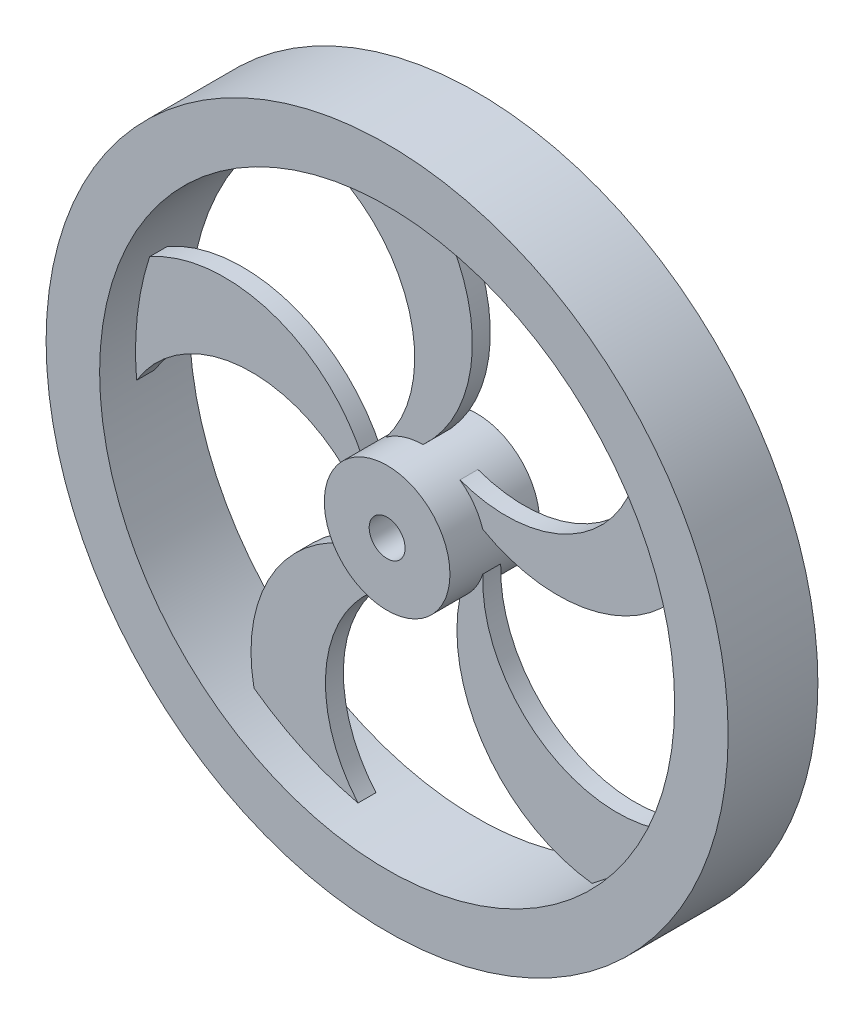
SolidWorks part; units mm, degrees
ref_plane "Front Plane" through (0, 0, 0) normal (0, 0, 1) x (1, 0, 0)
ref_plane "Top Plane" through (0, 0, 0) normal (0, 1, 0) x (1, 0, 0)
ref_plane "Right Plane" through (0, 0, 0) normal (1, 0, 0) x (0, 0, -1)
sketch "Sketch1" plane through (0, 0, 0) normal (0, 0, 1) x (1, 0, 0)
  circle A0 centre (0, 0) radius 7
  circle A1 centre (0, 0) radius 38
  circle A3 centre (0, 0) radius 2
  arc A4 (0, 7) -> (0, 32.0365) centre (-11.5019, 19.5183) ccw
  arc A5 (-4.1101, 5.6663) -> (-12.4811, 29.5053) centre (-15.9263, 14.9063) ccw
  arc A6 (6.6574, 2.1631) -> (30.4685, 9.8998) centre (15.0087, 16.9704) ccw
  arc A7 (4.1189, 5.6599) -> (24.2043, 20.9879) centre (9.2552, 19.7531) ccw
  arc A8 (4.1145, -5.6631) -> (18.8306, -25.9181) centre (20.7778, -9.03) ccw
  arc A9 (6.6557, -2.1683) -> (27.4402, -16.534) centre (21.6464, -2.6982) ccw
  arc A10 (-4.1145, -5.6631) -> (-18.8306, -25.9181) centre (-2.1673, -22.5512) ccw
  arc A11 (-0.0054, -7) -> (-7.2453, -31.2065) centre (4.123, -21.4207) ccw
  arc A12 (-6.6574, 2.1631) -> (-30.4685, 9.8998) centre (-22.1172, -4.9075) ccw
  arc A13 (-6.6591, -2.158) -> (-31.918, -2.7526) centre (-19.0982, -10.5406) ccw
  circle A14 centre (0, 0) radius 32.0365
  point P39 (0, 0)
  dimension "D1" = 5
  dimension "D2" = 76
  dimension "D3" = 5.9635
  dimension "D4" = 64.073
  dimension "D5" = 14
  dimension "D6" = 4
extrude "Boss-Extrude1" add sketch "Sketch1" along normal mid plane 10 contours A1 | A0 A3 region at (6.7179, -1.0667, 0) region at (-36.9252, 0, 0)
extrude "Boss-Extrude2" add sketch "Sketch1<4>" along normal mid plane 2 contours A12 A14 A13 A0 | A4 A14 A5 A0 | A6 A14 A7 A0 | A8 A14 A9 A0 | A10 A14 A11 A0 region at (20.5665, 7.1227, 0) region at (13.1295, -17.3588, 0) region at (-0.4187, 21.7609, 0) region at (-12.452, -17.8511, 0) region at (-20.8253, 6.3262, 0)
sketch "Sketch1<4>" plane through (0, 0, 0) normal (0, 0, 1) x (1, 0, 0) same geometry as "Sketch1"
